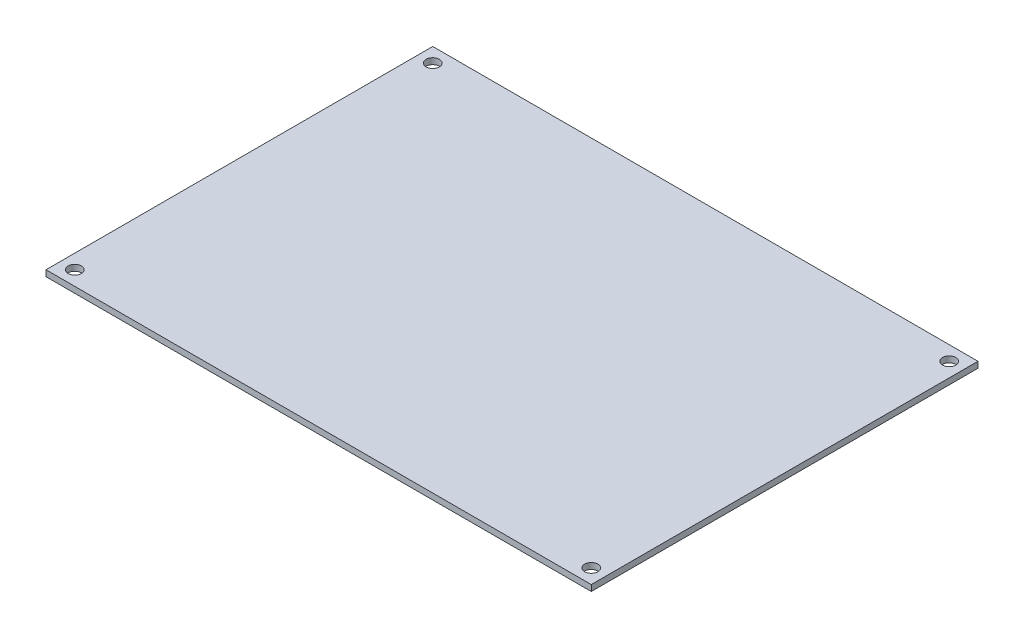
SolidWorks part; units mm, degrees
ref_plane "Front Plane" through (0, 0, 0) normal (0, 0, 1) x (1, 0, 0)
ref_plane "Top Plane" through (0, 0, 0) normal (0, 1, 0) x (1, 0, 0)
ref_plane "Right Plane" through (0, 0, 0) normal (1, 0, 0) x (0, 0, -1)
sketch "Sketch1" plane through (0, 0, 0) normal (0, 1, 0) x (1, 0, 0)
  line L1 (0, 0) -> (144.145, 0)
  line L2 (0, 0) -> (0, 102.235)
  line L3 (0, 102.235) -> (144.145, 102.235)
  line L4 (144.145, 0) -> (144.145, 102.235)
  circle A0 centre (3.815, 98.42) radius 1.7526
  circle A1 centre (140.33, 98.42) radius 1.7526
  circle A2 centre (140.33, 3.815) radius 1.7526
  circle A3 centre (3.815, 3.815) radius 1.7526
  point P13 (0, 0)
  point P14 (0, 0)
  point P15 (0, 0)
  point P16 (0, 0)
  point P17 (0, 0)
  dimension "D3" = 3.5052
  dimension "D1" = 144.145
  dimension "D2" = 102.235
  dimension "D4" = 3.815
  dimension "D5" = 3.815
  dimension "D6" = 3.815
  dimension "D7" = 3.815
extrude "Boss-Extrude1" add sketch "Sketch1" along normal blind 1.6
